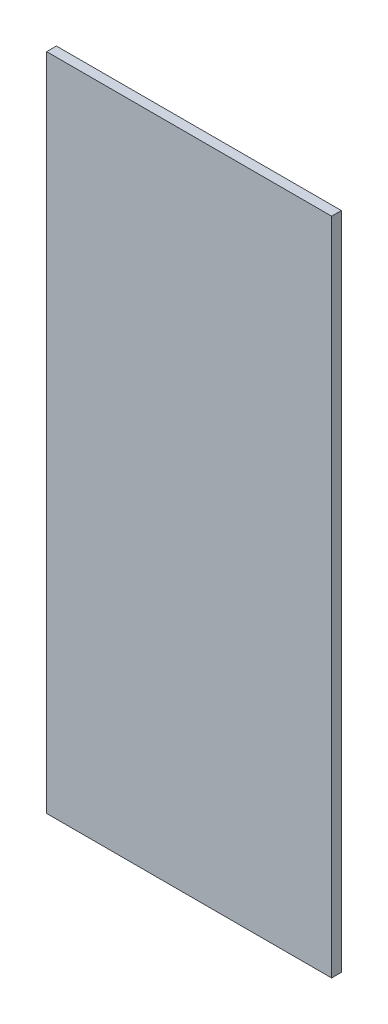
SolidWorks part; units mm, degrees
material "PC High Viscosity"
ref_plane "Front Plane" through (0, 0, 0) normal (0, 0, 1) x (1, 0, 0)
ref_plane "Top Plane" through (0, 0, 0) normal (0, 1, 0) x (1, 0, 0)
ref_plane "Right Plane" through (0, 0, 0) normal (1, 0, 0) x (0, 0, -1)
sketch "Sketch1" plane through (0, 0, 0) normal (0, 0, 1) x (1, 0, 0)
  line L1 (-73, -169) -> (73, -169)
  line L2 (-73, -169) -> (-73, 169)
  line L3 (-73, 169) -> (73, 169)
  line L4 (73, -169) -> (73, 169)
  line L5 (-73, -169) -> (73, 169) construction
  line L6 (-73, 169) -> (73, -169) construction
  point P0 (0, 0)
  dimension "D1" = 146
  dimension "D2" = 338
extrude "Boss-Extrude1" add sketch "Sketch1" along normal mid plane 5
sketch "Sketch2" plane through (0, 0, 2.5) normal (0, 0, 1) x (1, 0, 0)
  line L0 (106, 171) -> (104, 171) construction
  line L1 (-155.214, 211.8255) -> (203.9552, 211.8255)
  line L2 (-155.214, 211.8255) -> (-155.214, 171)
  line L3 (-155.214, 171) -> (203.9552, 171)
  line L4 (203.9552, 211.8255) -> (203.9552, 171)
extrude "Cut-Extrude1" [suppressed] cut sketch "Sketch2" against normal through all
